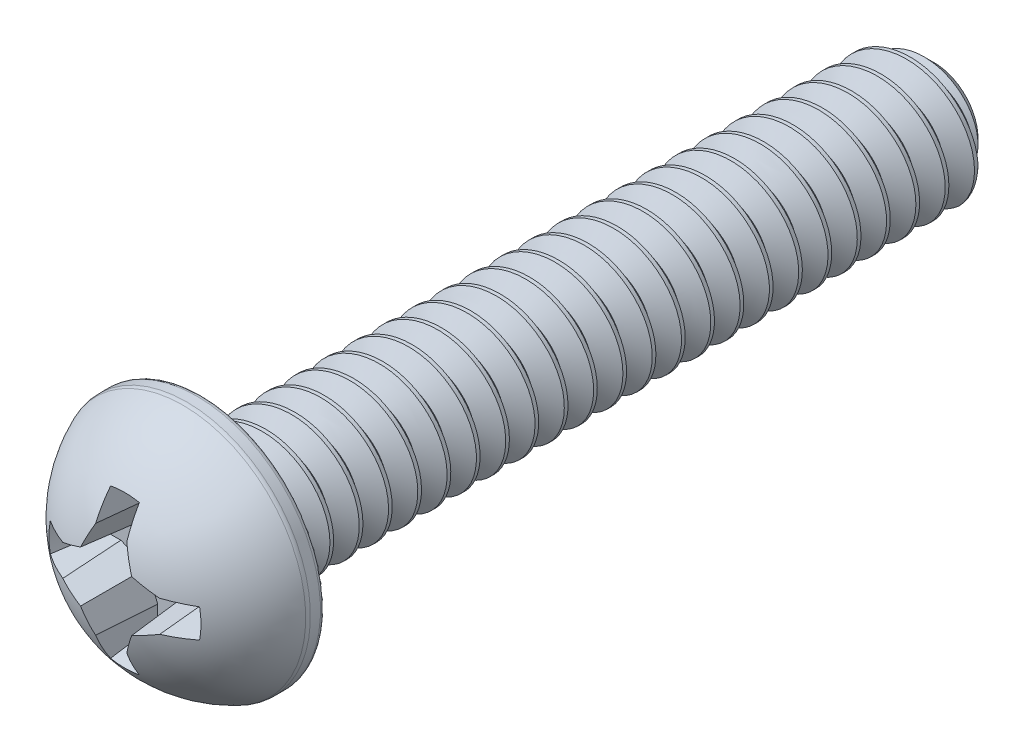
SolidWorks part; units mm, degrees
ref_plane "Front" through (0, 0, 0) normal (0, 0, 1) x (1, 0, 0)
ref_plane "Top" through (0, 0, 0) normal (0, 1, 0) x (1, 0, 0)
ref_plane "Right" through (0, 0, 0) normal (1, 0, 0) x (0, 0, -1)
sketch "Sketch1" plane through (0, 0, 0) normal (0, 0, 1) x (1, 0, 0)
  circle A0 centre (0, 0) radius 2.6797
  dimension "Head Dia" = 5.3594
extrude "Extrude3" add sketch "Sketch1" along normal blind 2.1844
sketch "Sketch11" plane through (0, 0, 0) normal (1, 0, 0) x (0, 0, -1)
  line L0 (0, 0) -> (-2.4384, 0) construction
  line L4 (-2.1844, 2.6797) -> (-2.1844, -2.6797) construction
  line L5 (-2.4384, 3.1064) -> (0, 3.1064)
  line L7 (0, 3.1064) -> (0, 2.5705)
  line L8 (-0.3277, 2.6797) -> (-0.1092, 2.6797)
  line L9 (0, -2.6797) -> (0, 2.6797) construction
  line L11 (0, 2.6797) -> (-2.1844, 2.6797) construction
  line L13 (-2.1844, 0) -> (-2.4384, 0)
  line L14 (-2.4384, 0) -> (-2.4384, 3.1064)
  arc A0 (-0.412, 2.6628) -> (-2.1844, 0) centre (0.702, 0) ccw
  arc A1 (-0.1092, 2.6797) -> (0, 2.5705) centre (-0.1092, 2.5705) cw
  arc A2 (-0.412, 2.6628) -> (-0.3277, 2.6797) centre (-0.3277, 2.4613) cw
  dimension "D2" = 0.1092
  dimension "D4" = 0.2184
  dimension "D3" = 0.254
  dimension "D1" = 0.2184
  dimension "D5" = 0.5359
revolve "Cut-Revolve3" cut sketch "Sketch11" angle 360 about L0
sketch "Sketch4" plane through (0, 0, 0) normal (1, 0, 0) x (0, 0, -1)
  line L0 (0, 0) -> (15.875, 0)
  line L3 (15.875, 0) -> (15.875, 1.4224)
  line L4 (15.875, 1.4224) -> (0, 1.4224)
  line L6 (0, 1.4224) -> (0, 0)
  line L9 (15.875, 1.4224) -> (15.875, -1.4224) construction
  dimension "length" = 15.875
  dimension "dia" = 2.8448
revolve "Revolve1" add sketch "Sketch4" angle 360 about L0
chamfer "Chamfer1" distance 0.4763 angle 45 1 edges at (1.4224, 0, -15.875)
sketch "Sketch13" plane through (0, 0, -15.875) normal (0, 0, -1) x (-1, 0, 0)
  circle A2 centre (0, 0) radius 1.4224
curve "Helix/Spiral1" pitch 0.635 height 17.78 turns 28
sketch "Sketch14" plane through (0, 0, 0) normal (1, 0, 0) x (0, 0, -1)
  line L0 (15.875, 1.4224) -> (16.4306, 1.4224)
  line L1 (16.4306, 1.4224) -> (16.1925, 0.9928)
  line L2 (16.1925, 0.9928) -> (16.1131, 0.9928)
  line L3 (16.1131, 0.9928) -> (15.875, 1.4224)
  line L4 (15.9941, 1.2076) -> (16.3116, 1.2076) construction
  dimension "D1" = 0.0794
  dimension "D2" = 58
  dimension "D3" = 0.3175
sweep "Cut-Sweep1" cut profiles "Sketch14" path "Helix/Spiral1"
ref_plane "Plane1" through (0, 0, 22.225) normal (0, 0, -1) x (-1, 0, 0)
sketch "Sketch29" [suppressed] plane through (0, 0, -38.1) normal (0, 0, -1) x (-1, 0, 0)
  circle A0 centre (0, 0) radius 4.7625 construction
  circle A1 centre (0, 0) radius 4.7625
  point P3 (0, -4.7625)
extrude "Extrude11" [suppressed] add sketch "Sketch29" against normal up to surface (38.1 mm away)
sketch "Sketch26" plane through (0, 0, 0) normal (0, 0, 1) x (1, 0, 0)
  circle A1 centre (0, 0) radius 0.5461
  dimension "D1" = 1.0922
extrude "Extrude8" add sketch "Sketch26" along normal up to surface (2.1323 mm away)
ref_plane "Plane2" through (0, 0, 2.1844) normal (0, 0, 1) x (1, 0, 0)
sketch "Sketch12" plane through (0, 0, 2.1844) normal (0, 0, 1) x (1, 0, 0)
  line L0 (0, 0) -> (0.3573, 0.3573) construction
  line L1 (0, 0) -> (0, -1.1128) construction
  line L2 (1.7504, 0.3573) -> (1.0538, 0.3573)
  line L3 (0, 1.7865) -> (0, 2.6797) construction
  line L8 (0.3573, 1.0538) -> (0.3573, 1.7504)
  line L9 (0.3573, 0.3573) -> (1.0538, 1.0538) construction
  line L10 (1.0538, 0.3573) -> (0.5613, 0.5613)
  line L11 (0.5613, 0.5613) -> (0.3573, 1.0538)
  line L12 (1.0538, 0.3573) -> (0.3573, 0.3573) construction
  line L13 (0.3573, 1.0538) -> (0.3573, 0.3573) construction
  line L14 (0, 0) -> (0, 1.7865)
  line L15 (0, 0) -> (1.7865, 0)
  circle A1 centre (0, 0) radius 2.6797 construction
  arc A2 (1.7865, 0) -> (1.7504, 0.3573) centre (0, 0) ccw
  arc A3 (0.3573, 1.7504) -> (0, 1.7865) centre (0, 0) ccw
  circle A5 centre (0, 0) radius 1.1128 construction
  arc A6 (1.0538, 0.3573) -> (0.3573, 1.0538) centre (1.0538, 1.0538) cw construction
  dimension "Phillips Dia" = 3.5729
  dimension "Phillips Width" = 0.7146
  dimension "D1" = 0.8932
extrude "Cut-Extrude3" cut sketch "Sketch12" against normal blind 1.4563
pattern_circular "CirPattern1" count 4 over 360 about axis through (0, 0, 0) along (0, 0, 1) of "Cut-Extrude3"
draft "Draft1" type of draft neutral plane draft angle 15 neutral plane "Plane2" faces to draft 4 face at (-1.7684, 0, 1.1466) face at (0, -1.7684, 1.1466) face at (1.7684, 0, 1.1466) face at (0, 1.7684, 1.1466) neutral plane through (0, 0, 2.1844) neutral plane normal (0, 0, 1) parameters "D1"=15
draft "Draft2" type of draft neutral plane draft angle 5 neutral plane "Plane2" faces to draft 16 face at (0.3573, 1.2362, 1.1577) face at (0.459, 0.8082, 1.3759) face at (0.8082, 0.459, 1.3759) face at (1.2362, 0.3573, 1.1577) face at (1.2362, -0.3573, 1.1577) face at (0.8082, -0.459, 1.3759) face at (0.459, -0.8082, 1.3759) face at (0.3573, -1.2362, 1.1577) face at (-0.3573, -1.2362, 1.1577) face at (-0.459, -0.8082, 1.3759) face at (-0.8082, -0.459, 1.3759) face at (-1.2362, -0.3573, 1.1577) face at (-1.2362, 0.3573, 1.1577) face at (-0.8082, 0.459, 1.3759) face at (-0.459, 0.8082, 1.3759) face at (-0.3573, 1.2362, 1.1577) neutral plane through (0, 0, 2.1844) neutral plane normal (0, 0, 1) parameters "D1"=5
sketch "Sketch18" plane through (0, 0, 0) normal (1, 0, 0) x (0, 0, -1)
  line L1 (15.875, 1.4224) -> (0, 1.4224) construction
  point P0 (14.9225, -1.4224)
  point P1 (15.24, 1.4224)
  point P2 (-2.1844, 0.5613)
  dimension "D1" = 0.635
  dimension "D2" = 0.9525
equation "\"Phillips Dia@Sketch12\"=\"Head Dia@Sketch1\"/1.5"
equation "\"Phillips Width@Sketch12\"=\"Phillips Dia@Sketch12\"/5"
equation "\"Phillips Depth@Cut-Extrude3\"= \"Head Ht@Extrude3\" / 1.5"
equation "\"D3@Helix/Spiral1\" = \"length@Sketch4\" + \"D4@Helix/Spiral1\" + .05"
equation "\"D1@Sketch14\" = \"D4@Helix/Spiral1\" * .125"
equation "\"D3@Sketch14\" = \"D4@Helix/Spiral1\" * .5"
equation "\"D1@Sketch11\" = \"Head Ht@Extrude3\" / 10"
equation "\"D2@Sketch11\" = \"D1@Sketch11\" / 2"
equation "\"D4@Sketch11\" = \"D1@Sketch11\""
equation "\"D5@Sketch11\" = \"Head Dia@Sketch1\" / 10"
equation "\"D1@Chamfer1\" = \"D4@Helix/Spiral1\" * .75"
equation "\"D1@Sketch18\" = \"D4@Helix/Spiral1\""
equation "\"D2@Sketch18\" = \"D4@Helix/Spiral1\" * 1.5"
